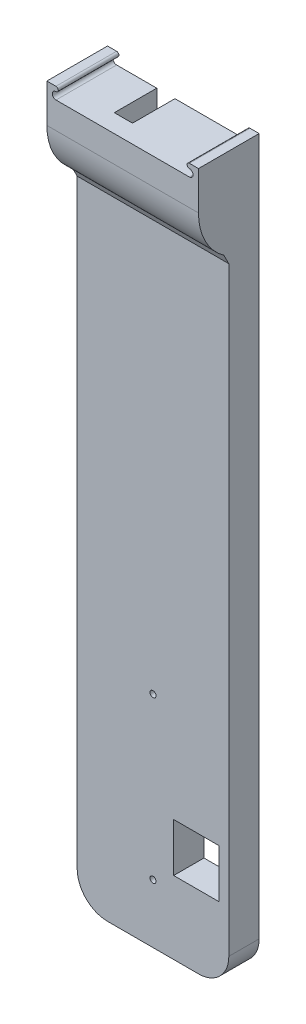
SolidWorks part; units mm, degrees
ref_plane "Přední rovina" through (0, 0, 0) normal (0, 0, 1) x (1, 0, 0)
ref_plane "Horní rovina" through (0, 0, 0) normal (0, 1, 0) x (1, 0, 0)
ref_plane "Pravá rovina" through (0, 0, 0) normal (1, 0, 0) x (0, 0, -1)
sketch "Skica1" plane through (0, 0, 0) normal (0, 0, 1) x (1, 0, 0)
  line L1 (0, 0) -> (25, 0)
  line L2 (0, 0) -> (0, 120)
  line L3 (0, 120) -> (25, 120)
  line L4 (25, 0) -> (25, 120)
  dimension "D1" = 120
  dimension "D2" = 25
extrude "Přidat vysunutím1" add sketch "Skica1" along normal blind 5
sketch "Skica2" plane through (0, 0, 0) normal (0, 0, -1) x (-1, 0, 0)
  line L0 (0, 120) -> (0, 0) construction
  line L1 (-25, 120) -> (0, 120)
  line L2 (-25, 120) -> (-25, 105)
  line L3 (-25, 105) -> (0, 105)
  line L4 (0, 120) -> (0, 105)
  dimension "D1" = 15
extrude "Přidat vysunutím2" add sketch "Skica2" against normal blind 10
fillet "Zaoblit5" radius 5 1 edges at (25, 0, 2.5)
fillet "Zaoblit6" radius 5 1 edges at (0, 0, 2.5)
sketch "Skica3" plane through (0, 0, 10) normal (0, 0, 1) x (1, 0, 0)
  line L0 (1.5, 118.04) -> (23.5, 118.04)
  line L1 (0, 120) -> (25, 120) construction
  line L4 (1.5, 120) -> (23.5, 120)
  line L5 (0, 105) -> (0, 120) construction
  line L6 (25, 120) -> (25, 105) construction
  arc A0 (23.5, 118.04) -> (23.5, 119.24) centre (23.5, 118.64) ccw
  arc A1 (23.5, 119.24) -> (23.5, 120) centre (23.5, 119.62) cw
  arc A2 (1.5, 118.04) -> (1.5, 119.24) centre (1.5, 118.64) cw
  arc A3 (1.5, 119.24) -> (1.5, 120) centre (1.5, 119.62) ccw
  dimension "D1" = 0.6
  dimension "D2" = 0.6
  dimension "D3" = 0.38
  dimension "D4" = 0.38
  dimension "D5" = 1.5
  dimension "D6" = 1.5
  dimension "D7" = 1.96
extrude "Odebrat vysunutím2" cut sketch "Skica3" against normal blind 20
fillet "Zaoblit7" radius 10 1 edges at (12.5, 105, 10)
fillet "Zaoblit8" radius 2 1 edges at (12.5, 105, 5) profile chamfer
sketch "Skica4" plane through (0, 118.04, 0) normal (0, 1, 0) x (1, 0, 0)
  line L0 (1.5, 0) -> (23.5, 0) construction
  line L1 (8.12, 0) -> (11.12, 0)
  line L2 (8.12, 0) -> (8.12, -7)
  line L3 (8.12, -7) -> (11.12, -7)
  line L4 (11.12, 0) -> (11.12, -7)
  line L5 (23.12, 0) -> (23.12, -10) construction
  dimension "D1" = 0
  dimension "D2" = 7
  dimension "D3" = 3
  dimension "D4" = 12
extrude "Odebrat vysunutím3" cut sketch "Skica4" against normal blind 4
sketch "Skica5" plane through (0, 0, 0) normal (0, 0, 1) x (1, 0, 0)
  line L0 (9, 21) -> (16, 21)
  line L1 (16, 21) -> (14, 43)
  line L3 (11, 43) -> (9, 21)
  line L4 (11, 43) -> (14, 43)
  line L5 (9, 21) -> (10.5, 5)
  line L6 (10.5, 5) -> (14.5, 5)
  line L7 (14.5, 5) -> (16, 21)
  line L9 (5, 0) -> (20, 0) construction
  line L10 (5.5, 24) -> (19.5, 24)
  line L11 (5.5, 24) -> (5.5, 20)
  line L12 (5.5, 20) -> (19.5, 20)
  line L13 (19.5, 24) -> (19.5, 20)
  arc A0 (5.5, 24) -> (5.5, 20) centre (5.5, 22) ccw
  arc A1 (19.5, 24) -> (19.5, 20) centre (19.5, 22) cw
  point P2 (12.5, 43)
  point P5 (12.5, 21)
  point P6 (12.5, 5)
  point P11 (12.5, 0)
  point P16 (12.5, 24)
  dimension "D1" = 7
  dimension "D2" = 3
  dimension "D3" = 22
  dimension "D4" = 16
  dimension "D5" = 5
  dimension "D6" = 4
  dimension "D7" = 19
  dimension "D8" = 14
  dimension "D9" = 4
extrude "Odebrat vysunutím4" cut sketch "Skica5" along normal blind 2 contours L3 L10 L1 L4 | L11 A0 | L11 L12 L5 L3 L10 | L10 L3 L0 L1 | L5 L12 L7 L0 | L13 L10 L1 L7 L12 | A1 L13 | L12 L5 L6 L7 region at (12.5, 22.4797, 0) region at (7.3079, 22.0229, 0) region at (12.5, 20.5023, 0) region at (17.6921, 22.0229, 0) region at (12.5, 32.3429, 0) region at (12.5, 13.1503, 0) region at (4.6512, 22, 0) region at (20.3488, 22, 0)
sketch "Skica7" plane through (0, 0, 2) normal (0, 0, -1) x (-1, 0, 0)
  line L0 (-11, 43) -> (-14, 43) construction
  line L1 (-21.5, 22) -> (-3.5, 22) construction
  circle A0 centre (-12.5, 36.2) radius 0.5
  circle A1 centre (-12.5, 9.7) radius 0.5
  arc A2 (-19.5, 24) -> (-19.5, 20) centre (-19.5, 22) ccw construction
  arc A3 (-5.5, 20) -> (-5.5, 24) centre (-5.5, 22) ccw construction
  point P9 (-12.5, 43)
  dimension "D1" = 1
  dimension "D2" = 1
  dimension "D4" = 12.3
  dimension "D3" = 14.2
extrude "Odebrat vysunutím5" cut sketch "Skica7" along normal offset from surface (2.8 mm away) 0.2 from surface up to face at (12.5, 22.6667, 2) starting at face at (12.5, 35.9593, 5)
sketch "Skica8" plane through (0, 0, 2) normal (0, 0, -1) x (-1, 0, 0)
  line L0 (-12.5, 43) -> (-12.5, 5) construction
  line L1 (-11, 43) -> (-14, 43) construction
  line L2 (-10.5, 5) -> (-14.5, 5) construction
  line L3 (-21.5, 22) -> (-3.5, 22) construction
  circle A0 centre (-12.5, 22) radius 3.75
  arc A1 (-19.5, 24) -> (-19.5, 20) centre (-19.5, 22) ccw construction
  arc A2 (-5.5, 20) -> (-5.5, 24) centre (-5.5, 22) ccw construction
  dimension "D3" = 7.5
  dimension "D1" = 0
  dimension "D2" = 0
extrude "Odebrat vysunutím6" cut sketch "Skica8" against normal blind 2
sketch "Skica9" plane through (0, 0, 0) normal (0, 0, -1) x (-1, 0, 0)
  line L1 (-15.9062, 20) -> (-23.4063, 20)
  line L2 (-15.9062, 20) -> (-15.9062, 12)
  line L3 (-15.9062, 12) -> (-23.4062, 12)
  line L4 (-23.4063, 20) -> (-23.4062, 12)
  dimension "D1" = 7.5
  dimension "D2" = 8
extrude "Odebrat vysunutím7" cut sketch "Skica9" against normal through all
